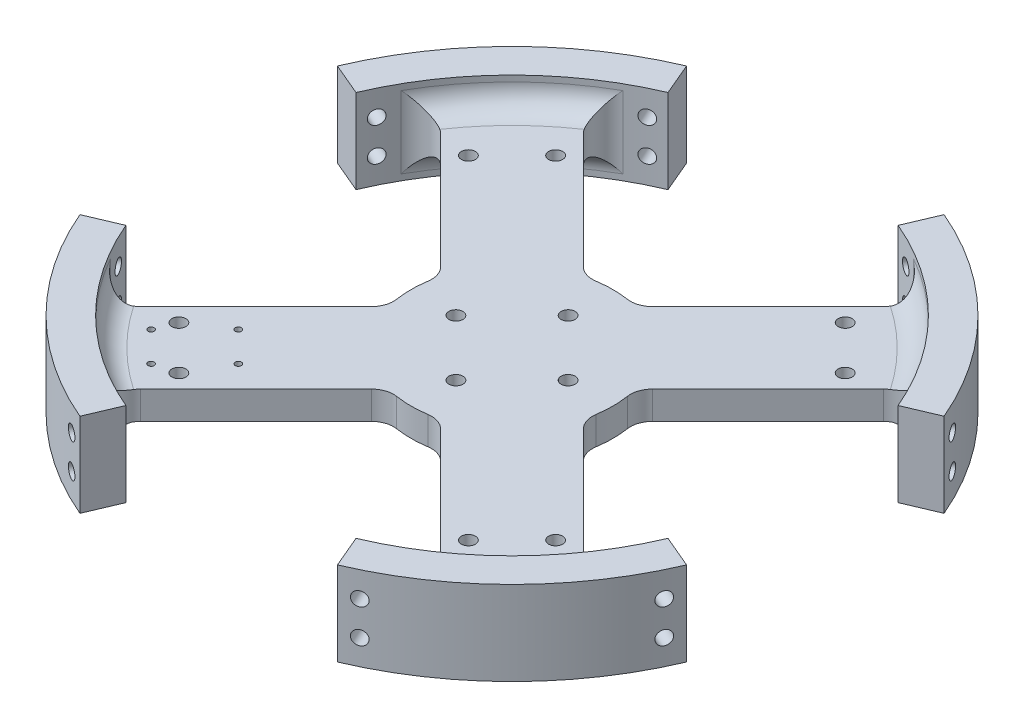
SolidWorks part; units mm, degrees
other "DetailItem1"
other "DetailItem2"
other "DetailItem3"
other "DetailItem4"
other "DetailItem5"
other "DetailItem6"
other "DetailItem7"
other "DetailItem8"
other "Weld Folder"
ref_plane "Front Plane" through (0, 0, 0) normal (0, 0, 1) x (1, 0, 0)
ref_plane "Top Plane" through (0, 0, 0) normal (0, 1, 0) x (1, 0, 0)
ref_plane "Right Plane" through (0, 0, 0) normal (1, 0, 0) x (0, 0, -1)
sketch "Sketch1" plane through (0, 0, 0) normal (0, 1, 0) x (1, 0, 0)
  line L0 (0, 0) -> (-105.518, 105.518) construction
  line L1 (0, 0) -> (0, -184.2319) construction
  line L2 (0, 0) -> (-52.104, 122.7493) construction
  line L3 (-52.104, 122.7493) -> (-58.3069, 137.3623)
  line L4 (0, 0) -> (-122.7493, 52.104) construction
  line L5 (-122.7493, 52.104) -> (-137.3623, 58.3069)
  line L6 (122.7493, 52.104) -> (137.3623, 58.3069)
  line L7 (52.104, 122.7493) -> (58.3069, 137.3623)
  line L8 (0, 0) -> (190.02, 0) construction
  line L9 (122.7493, -52.104) -> (137.3623, -58.3069)
  line L10 (52.104, -122.7493) -> (58.3069, -137.3623)
  line L11 (-52.104, -122.7493) -> (-58.3069, -137.3623)
  line L12 (-122.7493, -52.104) -> (-137.3623, -58.3069)
  arc A0 (-137.3623, -58.3069) -> (-58.3069, -137.3623) centre (0, 0) ccw
  arc A1 (-122.7493, -52.104) -> (-52.104, -122.7493) centre (0, 0) ccw
  arc A2 (-58.3069, 137.3623) -> (-137.3623, 58.3069) centre (0, 0) ccw
  arc A3 (-52.104, 122.7493) -> (-122.7493, 52.104) centre (0, 0) ccw
  arc A4 (137.3623, 58.3069) -> (58.3069, 137.3623) centre (0, 0) ccw
  arc A5 (122.7493, 52.104) -> (52.104, 122.7493) centre (0, 0) ccw
  arc A6 (58.3069, -137.3623) -> (137.3623, -58.3069) centre (0, 0) ccw
  arc A7 (52.104, -122.7493) -> (122.7493, -52.104) centre (0, 0) ccw
  dimension "D1" = 298.45
  dimension "D2" = 266.7
  dimension "D3" = 45
  dimension "D4" = 22
extrude "Boss-Extrude1" add sketch "Sketch1" along normal blind 25.4 and the other way blind 12.7
sketch "Sketch5" plane through (0, 0, 0) normal (0, 1, 0) x (1, 0, 0)
  line L48 (-0.0346, 0.0346) -> (0.0346, -0.0346) construction
  line L53 (0, 0) -> (-94.2927, -94.2927) construction
  line L55 (-19.2429, 19.2429) -> (19.2429, -19.2429) construction
  line L56 (-11.8332, -44.1621) -> (-76.7324, -109.0613)
  line L58 (-44.1621, -11.8332) -> (-109.0613, -76.7324)
  line L59 (-44.2828, -76.6117) -> (-76.6117, -44.2828) construction
  line L60 (-44.1621, 11.8332) -> (-109.0613, 76.7324)
  line L61 (-11.8332, 44.1621) -> (-76.7324, 109.0613)
  line L62 (11.8332, 44.1621) -> (76.7324, 109.0613)
  line L63 (44.1621, 11.8332) -> (109.0613, 76.7324)
  line L64 (44.1621, -11.8332) -> (109.0613, -76.7324)
  line L65 (11.8332, -44.1621) -> (76.7324, -109.0613)
  arc A0 (-76.7324, -109.0613) -> (-109.0613, -76.7324) centre (0, 0) cw
  arc A1 (-44.1621, 11.8332) -> (-44.1621, -11.8332) centre (0, 0) ccw
  arc A2 (11.8332, 44.1621) -> (-11.8332, 44.1621) centre (0, 0) ccw
  arc A3 (-109.0613, 76.7324) -> (-76.7324, 109.0613) centre (0, 0) cw
  arc A4 (44.1621, -11.8332) -> (44.1621, 11.8332) centre (0, 0) ccw
  arc A5 (76.7324, 109.0613) -> (109.0613, 76.7324) centre (0, 0) cw
  arc A6 (-11.8332, -44.1621) -> (11.8332, -44.1621) centre (0, 0) ccw
  arc A7 (109.0613, -76.7324) -> (76.7324, -109.0613) centre (0, 0) cw
  point P32 (0, 0)
  dimension "D3" = 133.35
  dimension "D5" = 45.72
  dimension "D1" = 90
  dimension "D2" = 133.35
  dimension "D4" = 45.72
  dimension "D6" = 4
extrude "Boss-Extrude3" add sketch "Sketch5" along normal blind 12.7
sketch "Sketch6" plane through (0, 12.7, 0) normal (0, 1, 0) x (1, 0, 0)
  line L0 (0, 0) -> (-75.4342, -75.4342) construction
  line L1 (-75.4342, -75.4342) -> (-65.5559, -85.3124) construction
  line L3 (0, 174.0525) -> (0, -174.0525) construction
  line L4 (0, 0) -> (102.9231, 0) construction
  circle A27 centre (-65.5559, -85.3124) radius 3.175
  circle A46 centre (-85.3124, -65.5559) radius 3.175
  circle A64 centre (85.3124, -65.5559) radius 3.175
  circle A65 centre (65.5559, -85.3124) radius 3.175
  circle A66 centre (85.3124, 65.5559) radius 3.175
  circle A67 centre (65.5559, 85.3124) radius 3.175
  circle A68 centre (-85.3124, 65.5559) radius 3.175
  circle A69 centre (-65.5559, 85.3124) radius 3.175
  point P23 (0, 0)
  point P24 (0, 0)
  dimension "D2" = 6.35
  dimension "D1" = 13.97
  dimension "D3" = 106.68
  dimension "D4" = 45
extrude "Cut-Extrude2" cut sketch "Sketch6" against normal through all
fillet "Fillet6" radius 10 24 edges at (11.8332, 6.35, -44.1621) (-11.8332, 6.35, -44.1621) (-44.1621, 6.35, 11.8332) (-44.1621, 6.35, -11.8332) (11.8332, 6.35, 44.1621) (-11.8332, 6.35, 44.1621) (44.1621, 6.35, -11.8332) (44.1621, 6.35, 11.8332) (-76.7324, 6.35, -109.0613) (-94.2927, 0, -94.2927) (-109.0613, 6.35, -76.7324) (-94.2927, 12.7, -94.2927) (94.2927, 12.7, -94.2927) (109.0613, 6.35, -76.7324) (76.7324, 6.35, -109.0613) (94.2927, 0, -94.2927) (76.7324, 6.35, 109.0613) (94.2927, 0, 94.2927) (109.0613, 6.35, 76.7324) (94.2927, 12.7, 94.2927) (-94.2927, 0, 94.2927) (-109.0613, 6.35, 76.7324) (-76.7324, 6.35, 109.0613) (-94.2927, 12.7, 94.2927)
sketch "Sketch35" plane through (0, 0, 0) normal (0, 1, 0) x (1, 0, 0)
  line L0 (0, 0) -> (-94.2927, 94.2927) construction
  line L1 (0, 0) -> (-120.8561, 56.3561) construction
  line L2 (-94.2927, 94.2927) -> (-120.8561, 56.3561) construction
  line L3 (-94.2927, 94.2927) -> (-56.3561, 120.8561) construction
  line L4 (0, 0) -> (-56.3561, 120.8561) construction
  arc A0 (-52.104, 122.7493) -> (-122.7493, 52.104) centre (0, 0) ccw construction
  dimension "D1" = 20
ref_plane "Plane1" through (-135.2438, 0, -63.0652) normal (-0.9063, 0, -0.4226) x (-0.4226, 0, 0.9063)
sketch "Sketch36" plane through (-135.2438, 0, -63.0652) normal (-0.9063, 0, -0.4226) x (-0.4226, 0, 0.9063)
  line L0 (-2.4121, 13.97) -> (-2.4121, 25.4) construction
  line L1 (5.2079, 25.4) -> (-99.851, 25.4) construction
  line L2 (0, 25.4) -> (0, -12.7) construction
  line L4 (-2.4121, 13.97) -> (5.2079, 13.97) construction
  line L5 (5.2079, -12.7) -> (5.2079, 25.4) construction
  line L6 (-99.851, -12.7) -> (5.2079, -12.7) construction
  line L7 (0, 6.35) -> (-29.3536, 6.35) construction
  circle A0 centre (-2.4121, 13.97) radius 3.175
  circle A1 centre (-2.4121, -1.27) radius 3.175
  dimension "D3" = 6.35
  dimension "D1" = 7.62
  dimension "D2" = 11.43
  dimension "D4" = 1.27
ref_plane "Plane2" through (-63.0652, 0, -135.2438) normal (-0.4226, 0, -0.9063) x (-0.9063, 0, 0.4226)
sketch "Sketch39" plane through (-63.0652, 0, -135.2438) normal (-0.4226, 0, -0.9063) x (-0.9063, 0, 0.4226)
  line L0 (0, 25.4) -> (0, -12.7) construction
  line L2 (2.4121, 13.97) -> (2.4121, 25.4) construction
  line L3 (99.851, 25.4) -> (-5.2079, 25.4) construction
  line L4 (2.4121, 13.97) -> (-5.2079, 13.97) construction
  line L5 (-5.2079, -12.7) -> (-5.2079, 25.4) construction
  line L6 (-5.2079, -12.7) -> (99.851, -12.7) construction
  line L7 (0, 6.35) -> (11.7181, 6.35) construction
  circle A0 centre (2.4121, 13.97) radius 3.175
  circle A1 centre (2.4121, -1.27) radius 3.175
  dimension "D3" = 6.35
  dimension "D1" = 7.62
  dimension "D2" = 11.43
  dimension "D4" = 1.27
sketch "Sketch46" plane through (0, 0, 0) normal (0, -1, 0) x (1, 0, 0)
  line L0 (-68.7309, 85.3124) -> (-85.3124, 68.7309)
  line L1 (-85.3124, 68.7309) -> (-82.1374, 65.5559)
  line L2 (-82.1374, 65.5559) -> (-65.5559, 82.1374)
  line L3 (-65.5559, 82.1374) -> (-68.7309, 85.3124)
  line L5 (82.1374, 65.5559) -> (65.5559, 82.1374)
  line L6 (85.3124, 68.7309) -> (82.1374, 65.5559)
  line L7 (68.7309, 85.3124) -> (85.3124, 68.7309)
  line L8 (65.5559, 82.1374) -> (68.7309, 85.3124)
  line L10 (85.3124, -68.7309) -> (82.1374, -65.5559)
  line L11 (68.7309, -85.3124) -> (85.3124, -68.7309)
  line L12 (65.5559, -82.1374) -> (68.7309, -85.3124)
  line L13 (82.1374, -65.5559) -> (65.5559, -82.1374)
  line L14 (-82.1374, -65.5559) -> (-65.5559, -82.1374)
  line L15 (-85.3124, -68.7309) -> (-82.1374, -65.5559)
  line L16 (-68.7309, -85.3124) -> (-85.3124, -68.7309)
  line L17 (-65.5559, -82.1374) -> (-68.7309, -85.3124)
  circle A0 centre (-65.5559, 85.3124) radius 3.175 construction
  circle A1 centre (-85.3124, 65.5559) radius 3.175 construction
split line "Split Line4"
ref_plane "Plane4" through (-105.518, 0, -105.518) normal (-0.7071, 0, -0.7071) x (-0.7071, 0, 0.7071)
sketch "Sketch51" plane through (-105.518, 0, -105.518) normal (-0.7071, 0, -0.7071) x (-0.7071, 0, 0.7071)
  line L0 (0, 25.4) -> (0, 19.05) construction
  line L1 (55.9007, 25.4) -> (-55.9007, 25.4) construction
sketch "Sketch52" plane through (0, 12.7, 0) normal (0, 1, 0) x (1, 0, 0)
  line L1 (0, 0) -> (0, 25.4) construction
  circle A0 centre (0, 25.4) radius 3.175
  circle A1 centre (25.4, 0) radius 3.175
  circle A2 centre (-25.4, 0) radius 3.175
  circle A3 centre (0, -25.4) radius 3.175
  dimension "D1" = 6.35
  dimension "D3" = 76.6249
  dimension "D4" = 102.0249
  dimension "D5" = 127.4249
  dimension "D6" = 76.6249
  dimension "D7" = 102.0249
  dimension "D8" = 127.4249
extrude "Cut-Extrude5" cut sketch "Sketch52" against normal through all
sketch "Sketch53" plane through (0, 12.7, 0) normal (0, 1, 0) x (1, 0, 0)
  line L1 (-47.9838, -15.6549) -> (-100.2342, -67.9053) construction
  line L2 (15.6549, -47.9838) -> (67.9053, -100.2342) construction
  line L3 (-100.2342, 67.9053) -> (-47.9838, 15.6549) construction
  circle A0 centre (-75.4342, -88.0065) radius 1.397
  circle A1 centre (-55.6776, -68.2499) radius 1.397
  circle A2 centre (-88.9045, -74.5361) radius 1.397
  circle A3 centre (-69.148, -54.7796) radius 1.397
  dimension "D7" = 2.794
  dimension "D1" = 19.05
  dimension "D2" = 19.05
  dimension "D3" = 27.94
  dimension "D4" = 12.7
  dimension "D5" = 12.7
  dimension "D6" = 27.94
  dimension "D8" = 64.77
  dimension "D9" = 64.77
extrude "Cut-Extrude6" cut sketch "Sketch53" against normal up to next contours A0 | A1 | A3 | A2
extrude "Cut-Extrude7" cut sketch "Sketch39" against normal up to next
extrude "Cut-Extrude8" cut sketch "Sketch36" against normal up to next
pattern_circular "CirPattern1" count 4 over 360 about axis through (0, 12.7, 0) along (0, 1, 0) of "Cut-Extrude8", "Cut-Extrude7"
equation "\"Rocket Diameter\"= 12"
equation "\"Rocket Thickness\"= .25"
equation "\"D1@Sketch1\"=\"Rocket Diameter\"-.25"
equation "\"Plate_Mount\"= \"Rocket Diameter\" - 6 * \"Rocket Thickness\""
equation "\"Beam_Thickness\"= \"Rocket Diameter\" / 20"
equation "\"Cord Diameter\"=0.25"
equation "\"Center_Circle\"= \"Rocket Diameter\" / 12"
equation "\"D1@Sketch6\"=\"Beam_Thickness\"/2+\"Cord Diameter\""
equation "\"D2@Sketch6\"=\"Cord Diameter\""
equation "\"D3@Sketch6\"=\"Plate_Mount\"*2/5"
equation "\"Shear Pin Distance\"= 2"
equation "\"D2@Sketch1\"=\"Plate_Mount\""
equation "\"D2@Sketch5\"=\"Plate_Mount\"/2"
equation "\"D3@Sketch5\"=\"Plate_Mount\"/2"
equation "\"D4@Sketch5\"=\"Beam_Thickness\"*3"
equation "\"D5@Sketch5\"=\"Beam_Thickness\"*3"
equation "\"Center Radius\"= ( \"Beam_Thickness\" * 4 * .75 + .25 * ( \"Plate_Mount\" / 2 ) ) / 2"
